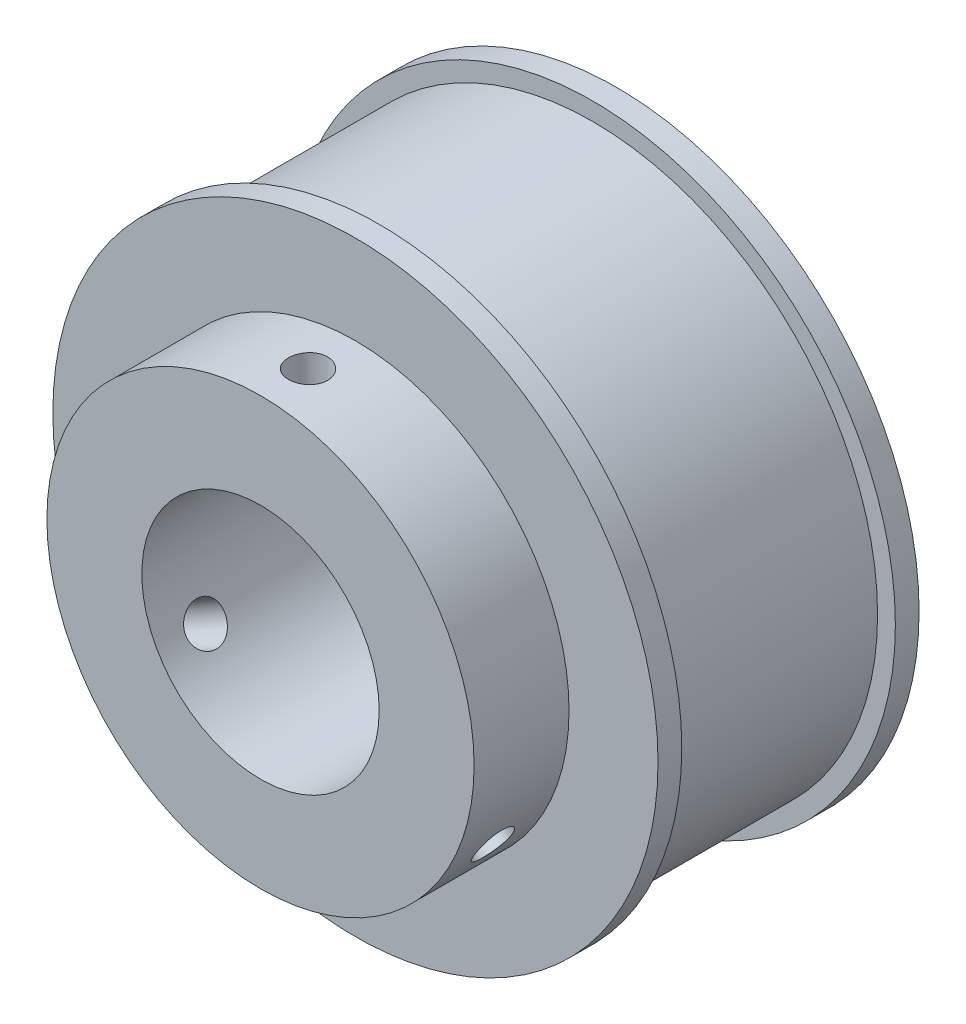
SolidWorks part; units mm, degrees
material "PA Type 6"
ref_plane "Front Plane" through (0, 0, 0) normal (0, 0, 1) x (1, 0, 0)
ref_plane "Top Plane" through (0, 0, 0) normal (0, 1, 0) x (1, 0, 0)
ref_plane "Right Plane" through (0, 0, 0) normal (1, 0, 0) x (0, 0, -1)
sketch "Sketch1" plane through (0, 0, 0) normal (0, 0, 1) x (1, 0, 0)
  circle A0 centre (0, 0) radius 24
  dimension "D1" = 48
extrude "Boss-Extrude1" add sketch "Sketch1" along normal blind 18
sketch "Sketch2" plane through (0, 0, 18) normal (0, 0, 1) x (1, 0, 0)
  circle A3 centre (0, 0) radius 25.5
  circle A4 centre (0, 0) radius 25.5
  dimension "D1" = 1.5
extrude "Boss-Extrude2" add sketch "Sketch2" along normal blind 2
extrude "Boss-Extrude3" add sketch "Sketch2<2>" against normal blind 2 from surface starting at face at (24, 0, 0)
sketch "Sketch2<2>" plane through (0, 0, 18) normal (0, 0, 1) x (1, 0, 0) same geometry as "Sketch2"
sketch "Sketch3" plane through (0, 0, 20) normal (0, 0, 1) x (1, 0, 0)
  point P0 (0, 0)
hole_wizard "Ø20.0mm Dowel Hole1" positions "Sketch3" profile "Sketch5" hole size "Ø20.0" standard "DIN" end condition through all
sketch "Sketch5" plane through (0, 0, 20) normal (1, 0, 0) x (0, -1, 0)
  line L0 (0, 0) -> (0, 22)
  line L1 (0, 22) -> (10, 22)
  line L2 (10, 22) -> (10, 0)
  line L5 (10, 0) -> (0, 0)
  line L11 (0, -6.35) -> (0, 107.95) construction
  dimension "Thru Hole Dia." = 20
  dimension "Thru Hole Depth" = 22
sketch "Sketch13" plane through (0, 0, 20) normal (0, 0, 1) x (1, 0, 0)
  circle A0 centre (0, 0) radius 10
  circle A1 centre (0, 0) radius 18
  dimension "D1" = 36
extrude "Boss-Extrude4" add sketch "Sketch13" along normal blind 8
sketch "Sketch15" plane through (0, 0, 0) normal (0, 1, 0) x (1, 0, 0)
  line L0 (-18, -20) -> (18, -20) construction
  point P0 (0, -24)
  dimension "D1" = 4
hole_wizard "Tap Drill for M4 Tap1" positions "Sketch15" profile "Sketch16" hole size "M4" standard "DIN" end condition through all
sketch "Sketch16" plane through (0, 0, 24) normal (1, 0, 0) x (0, 0, -1)
  line L0 (0, 0) -> (0, 25.5)
  line L1 (0, 25.5) -> (1.65, 25.5)
  line L2 (1.65, 25.5) -> (1.65, 0)
  line L5 (1.65, 0) -> (0, 0)
  line L11 (0, -6.35) -> (0, 107.95) construction
  dimension "Thru Hole Dia." = 3.3
  dimension "Thru Hole Depth" = 25.5
ref_axis "Axis1" through (0, 0, -2) along (0, 0, 1)
ref_plane "Plane4" through (-15.5885, -9, 0) normal (-0.866, -0.5, 0) x (0, 0, -1)
sketch "Sketch20" plane through (-15.5885, -9, 0) normal (-0.866, -0.5, 0) x (0, 0, -1)
  line L0 (2, 0) -> (-28, 0) construction
  line L1 (-20, 18) -> (-20, -18) construction
  point P0 (-24, 0)
  dimension "D1" = 4
hole_wizard "Tap Drill for M4 Tap3" positions "Sketch20" profile "Sketch21" hole size "M4" standard "DIN"
sketch "Sketch21" plane through (-15.5885, -9, 24) normal (0, 0, 1) x (0.5, -0.866, 0)
  line L0 (0, 0) -> (0, 17.8214)
  line L1 (0, 17.8214) -> (1.65, 16.83)
  line L2 (1.65, 16.83) -> (1.65, 0)
  line L5 (1.65, 0) -> (0, 0)
  line L10 (0, 17.8214) -> (-1.65, 16.83) construction
  line L11 (0, -6.35) -> (0, 107.95) construction
  dimension "Hole Dia." = 3.3
  dimension "Hole Depth" = 16.83
  dimension "Drill Angle" = 118
ref_plane "Plane5" through (15.5885, -9, 0) normal (0.866, -0.5, 0) x (0, 0, -1)
sketch "Sketch22" plane through (15.5885, -9, 0) normal (0.866, -0.5, 0) x (0, 0, -1)
  line L0 (2, 0) -> (-28, 0) construction
  line L1 (-20, 25.5) -> (-20, -25.5) construction
  point P0 (-24, 0)
  dimension "D1" = 4
hole_wizard "Tap Drill for M4 Tap4" positions "Sketch22" profile "Sketch23" hole size "M4" standard "DIN"
sketch "Sketch23" plane through (15.5885, -9, 24) normal (0, 0, 1) x (0.5, 0.866, 0)
  line L0 (0, 0) -> (0, 17.8214)
  line L1 (0, 17.8214) -> (1.65, 16.83)
  line L2 (1.65, 16.83) -> (1.65, 0)
  line L5 (1.65, 0) -> (0, 0)
  line L10 (0, 17.8214) -> (-1.65, 16.83) construction
  line L11 (0, -6.35) -> (0, 107.95) construction
  dimension "Hole Dia." = 3.3
  dimension "Hole Depth" = 16.83
  dimension "Drill Angle" = 118
